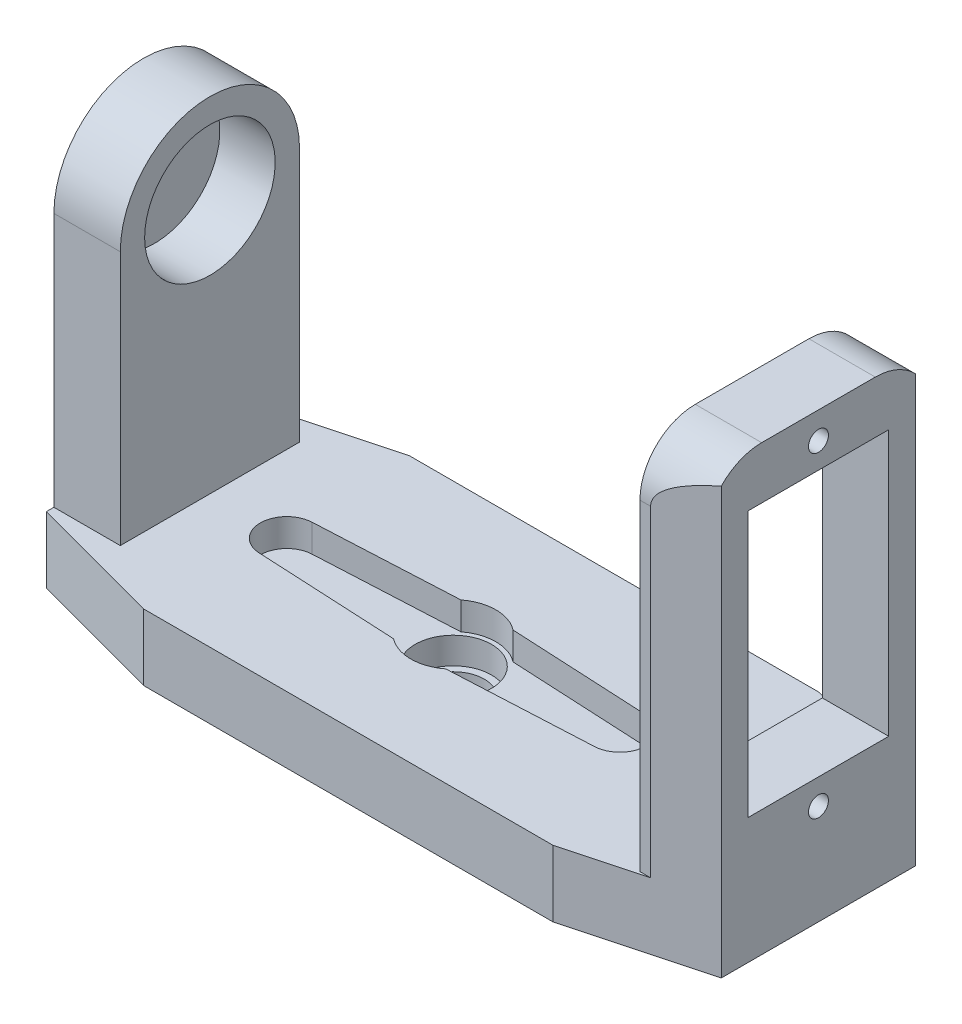
SolidWorks part; units mm, degrees
ref_plane "前视基准面" through (0, 0, 0) normal (0, 0, 1) x (1, 0, 0)
ref_plane "上视基准面" through (0, 0, 0) normal (0, 1, 0) x (1, 0, 0)
ref_plane "右视基准面" through (0, 0, 0) normal (1, 0, 0) x (0, 0, -1)
sketch "草图1" plane through (0, 0, 0) normal (0, 1, 0) x (1, 0, 0)
  line L0 (0, 0) -> (2.5, 0) construction
  line L1 (33, -12) -> (-28, -12)
  line L2 (33, -12) -> (33, 12)
  line L3 (33, 12) -> (-28, 12)
  line L4 (-28, -12) -> (-28, 12)
  line L5 (33, -12) -> (-28, 12) construction
  line L6 (33, 12) -> (-28, -12) construction
  point P0 (0, 0)
  dimension "D1" = 28
  dimension "D2" = 33
  dimension "D3" = 24
extrude "凸台-拉伸1" add sketch "草图1" along normal blind 6
sketch "草图2" plane through (-28, 0, 0) normal (-1, 0, 0) x (0, 0, 1)
  line L0 (-12, 6) -> (12, 6) construction
  line L1 (8.0991, 37.0991) -> (-8.0991, 37.0991)
  line L2 (8.0991, 37.0991) -> (8.0991, 6)
  line L3 (8.0991, 6) -> (-8.0991, 6)
  line L4 (-8.0991, 37.0991) -> (-8.0991, 6)
  line L5 (8.0991, 37.0991) -> (-8.0991, 6) construction
  line L6 (8.0991, 6) -> (-8.0991, 37.0991) construction
  line L7 (0, 21.5496) -> (0, 6) construction
  circle A0 centre (0, 29) radius 5.9
  circle A1 centre (0, 29) radius 8.0991 construction
  point P0 (0, 21.5496)
  dimension "D2" = 11.8
  dimension "D1" = 23
extrude "凸台-拉伸2" add sketch "草图2" against normal blind 6
sketch "草图8" plane through (-28, 0, 0) normal (-1, 0, 0) x (0, 0, 1)
  circle A1 centre (0, 29) radius 5.9 construction
  circle A2 centre (0, 29) radius 5.9
extrude "凸台-拉伸4" add sketch "草图8" against normal blind 1
fillet "圆角1" 2 edges at (-25, 37.0991, -8.0991) (-25, 37.0991, 8.0991) type full round first side face at (-25, 21.5496, -8.0991) second side face at (-25, 21.5496, 8.0991) middle face at (-25, 37.0991, 0)
sketch "草图3" plane through (33, 0, 0) normal (1, 0, 0) x (0, 0, -1)
  line L0 (0, 23.35) -> (18.2252, 23.35) construction
  line L1 (10.134, 40.0752) -> (-10.134, 40.0752)
  line L2 (10.134, 40.0752) -> (10.134, 6)
  line L3 (10.134, 6) -> (-10.134, 6)
  line L4 (-10.134, 40.0752) -> (-10.134, 6)
  line L5 (10.134, 40.0752) -> (-10.134, 6) construction
  line L6 (10.134, 6) -> (-10.134, 40.0752) construction
  line L7 (0, 23.35) -> (0, 0) construction
  line L8 (6.35, 35.35) -> (-6.35, 35.35)
  line L9 (6.35, 35.35) -> (6.35, 11.35)
  line L10 (6.35, 11.35) -> (-6.35, 11.35)
  line L11 (-6.35, 35.35) -> (-6.35, 11.35)
  line L12 (6.35, 35.35) -> (-6.35, 11.35) construction
  line L13 (6.35, 11.35) -> (-6.35, 35.35) construction
  line L17 (-12, 6) -> (12, 6) construction
  circle A0 centre (0, 29) radius 5.9 construction
  circle A1 centre (0, 29) radius 5.9 construction
  circle A2 centre (0, 9.05) radius 0.9
  circle A3 centre (0, 37.65) radius 0.9
  circle A4 centre (0, 29) radius 6.35 construction
  point P0 (0, 23.0376)
  point P7 (0, 23.35)
  dimension "D5" = 1.8
  dimension "D1" = 24
  dimension "D2" = 12.7
  dimension "D4" = 14.3
extrude "凸台-拉伸3" add sketch "草图3" against normal blind 6
fillet "圆角2" radius 5 2 edges at (30, 40.0752, 10.134) (30, 40.0752, -10.134)
sketch "草图4" plane through (-24, 6, 6) normal (0, -1, 0) x (-1, 0, 0)
  line L0 (-24, 6) -> (-8.95, 6) construction
  line L1 (-8.8493, 4.0025) -> (-21.7909, 3.35) construction
  line L2 (-21.7909, 8.65) -> (-8.8493, 7.9975) construction
  line L3 (-21.6414, 9.043) -> (-8.8291, 8.397)
  line L4 (-8.8291, 3.603) -> (-21.6414, 2.957)
  arc A0 (-21.7909, 8.65) -> (-21.7909, 3.35) centre (-24, 6) ccw construction
  arc A1 (-8.8493, 4.0025) -> (-8.8493, 7.9975) centre (-8.95, 6) ccw construction
  arc A2 (-8.8291, 3.603) -> (-8.8291, 8.397) centre (-8.95, 6) ccw
  arc A3 (-21.6414, 9.043) -> (-21.6414, 2.957) centre (-24, 6) ccw
  dimension "D1" = 6.9
  dimension "D2" = 4
  dimension "D3" = 20.5
  dimension "D4" = 5.3
  dimension "D5" = 0.4
extrude "切除-拉伸1" cut sketch "草图4" along normal blind 2.5
mirror "镜向1" about plane through (0, 0, 0) normal (1, 0, 0) of "切除-拉伸1"
sketch "草图5" plane through (0, 3.5, 0) normal (0, 1, 0) x (1, 0, 0)
  circle A0 centre (0, 0) radius 3.45
extrude "切除-拉伸2" cut sketch "草图5" against normal blind 2.4
chamfer "倒角1" distance 12 angle 15 4 edges at (33, 3, -12) (33, 3, 12) (-28, 3, 12) (-28, 3, -12) first distance on face at (2.5, 3, -12) first distance on face at (2.5, 3, 12)
sketch "草图6" plane through (0, 1.1, 0) normal (0, 1, 0) x (1, 0, 0)
  circle A0 centre (0, 0) radius 2.8
  dimension "D1" = 5.6
extrude "切除-拉伸3" cut sketch "草图6" against normal through all
